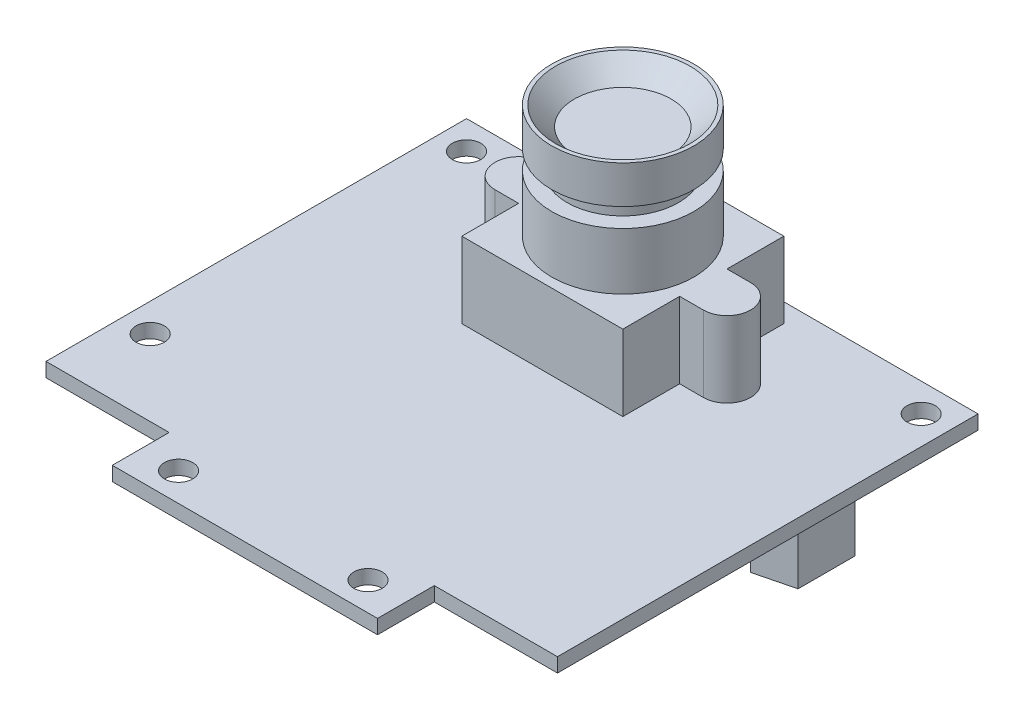
SolidWorks part; units mm, degrees
ref_plane "Front Plane" through (0, 0, 0) normal (0, 0, 1) x (1, 0, 0)
ref_plane "Top Plane" through (0, 0, 0) normal (0, 1, 0) x (1, 0, 0)
ref_plane "Right Plane" through (0, 0, 0) normal (1, 0, 0) x (0, 0, -1)
sketch "Sketch1" plane through (0, 0, 0) normal (0, 1, 0) x (1, 0, 0)
  line L1 (-27, 22.2) -> (27, 22.2)
  line L2 (-27, 22.2) -> (-27, -22.2)
  line L3 (-27, -22.2) -> (27, -22.2)
  line L4 (27, 22.2) -> (27, -22.2)
  line L5 (-27, 22.2) -> (27, -22.2) construction
  line L6 (-27, -22.2) -> (27, 22.2) construction
  line L7 (-14, -22.2) -> (14, -22.2)
  line L8 (-14, -22.2) -> (-14, -28.2)
  line L9 (-14, -28.2) -> (14, -28.2)
  line L10 (14, -22.2) -> (14, -28.2)
  point P0 (0, 0)
  dimension "D1" = 54
  dimension "D2" = 44.4
  dimension "D3" = 13
  dimension "D4" = 13
  dimension "D5" = 6
extrude "Boss-Extrude1" add sketch "Sketch1" along normal blind 1.5 contours L4 L1 L2 L3 | L10 L3 L8 L9 region at (0, 0, 0) region at (0, 0, 25.2)
sketch "Sketch2" plane through (0, 1.5, 0) normal (0, 1, 0) x (1, 0, 0)
  line L0 (-27, 22.2) -> (-27, -22.2) construction
  line L1 (-27, 22.2) -> (27, 22.2) construction
  line L2 (27, 22.2) -> (27, -22.2) construction
  line L3 (-27, -22.2) -> (-14, -22.2) construction
  line L4 (-14, -28.2) -> (14, -28.2) construction
  line L5 (-14, -22.2) -> (-14, -28.2) construction
  line L6 (14, -22.2) -> (14, -28.2) construction
  circle A0 centre (-24, 19.2) radius 1.5
  circle A1 centre (24, 19.2) radius 1.5
  circle A2 centre (-24, -14.2) radius 1.5
  circle A3 centre (-10, -25.2) radius 1.5
  circle A4 centre (10, -25.2) radius 1.5
  circle A5 centre (0, 11.7) radius 1
  dimension "D1" = 3
  dimension "D2" = 3
  dimension "D3" = 3
  dimension "D4" = 3
  dimension "D5" = 3
  dimension "D12" = 3
  dimension "D16" = 10.5
  dimension "D6" = 3
  dimension "D7" = 3
  dimension "D8" = 3
  dimension "D9" = 3
  dimension "D10" = 3
  dimension "D11" = 8
  dimension "D13" = 4
  dimension "D14" = 4
  dimension "D15" = 3
extrude "Cut-Extrude1" cut sketch "Sketch2" against normal blind 1.5
sketch "Sketch3" plane through (0, 1.5, 0) normal (0, 1, 0) x (1, 0, 0)
  line L0 (-27, 22.2) -> (27, 22.2) construction
  line L1 (-8.5, 20.2) -> (8.5, 20.2)
  line L2 (-8.5, 20.2) -> (-8.5, 14.2)
  line L3 (-8.5, 3.2) -> (8.5, 3.2)
  line L4 (8.5, 20.2) -> (8.5, 14.2)
  line L5 (-8.5, 20.2) -> (8.5, 3.2) construction
  line L6 (-8.5, 3.2) -> (8.5, 20.2) construction
  line L7 (0, 0) -> (0, 11.7) construction
  line L8 (-11, 11.7) -> (11, 11.7) construction
  line L9 (-11, 14.2) -> (-8.5, 14.2)
  line L10 (-11, 9.2) -> (-8.5, 9.2)
  line L11 (11, 14.2) -> (8.5, 14.2)
  line L12 (11, 9.2) -> (8.5, 9.2)
  line L13 (-8.5, 9.2) -> (-8.5, 3.2)
  line L14 (8.5, 9.2) -> (8.5, 3.2)
  arc A0 (-11, 14.2) -> (-11, 9.2) centre (-11, 11.7) ccw
  arc A1 (11, 9.2) -> (11, 14.2) centre (11, 11.7) ccw
  point P0 (0, 11.7)
  dimension "D1" = 2
  dimension "D2" = 17
  dimension "D3" = 17
extrude "Boss-Extrude2" add sketch "Sketch3" along normal blind 8
sketch "Sketch4" plane through (0, 9.5, 0) normal (0, 1, 0) x (1, 0, 0)
  line L0 (0, 20.2) -> (0, 3.2) construction
  line L1 (8.5, 20.2) -> (-8.5, 20.2) construction
  line L2 (-8.5, 3.2) -> (8.5, 3.2) construction
  line L3 (-13.5, 11.7) -> (13.5, 11.7) construction
  arc A0 (-11, 14.2) -> (-11, 9.2) centre (-11, 11.7) ccw construction
  arc A1 (11, 9.2) -> (11, 14.2) centre (11, 11.7) ccw construction
  circle A2 centre (0, 11.7) radius 7.5
  dimension "D1" = 15
extrude "Boss-Extrude3" add sketch "Sketch4" along normal blind 6
sketch "Sketch5" plane through (0, 15.5, 0) normal (0, 1, 0) x (1, 0, 0)
  circle A0 centre (0, 11.7) radius 5.8771
extrude "Boss-Extrude4" add sketch "Sketch5" along normal blind 2
sketch "Sketch6" plane through (0, 17.5, 0) normal (0, 1, 0) x (1, 0, 0)
  circle A0 centre (0, 11.7) radius 7.5
extrude "Boss-Extrude5" add sketch "Sketch6" along normal blind 4
sketch "Sketch7" plane through (0, 21.5, 0) normal (0, 1, 0) x (1, 0, 0)
  circle A0 centre (0, 11.7) radius 5.0974
extrude "Cut-Extrude3" cut sketch "Sketch7" against normal blind 2
chamfer "Chamfer1" distance 2 angle 45 1 edges at (0, 21.5, -6.6026)
sketch "Sketch8" plane through (0, 0, 0) normal (0, -1, 0) x (1, 0, 0)
  line L0 (18, -7.2) -> (18, -15.2)
  line L1 (18, -15.2) -> (22, -14.2)
  line L2 (22, -14.2) -> (22, -8.2)
  line L3 (22, -8.2) -> (18, -7.2)
  line L4 (27, -22.2) -> (27, 22.2) construction
  line L5 (-27, -22.2) -> (27, -22.2) construction
  dimension "D1" = 4
  dimension "D2" = 8
  dimension "D3" = 6
  dimension "D4" = 1
  dimension "D5" = 5
  dimension "D6" = 7
extrude "Boss-Extrude6" add sketch "Sketch8" along normal blind 10
sketch "Sketch9" plane through (0, 0, 0) normal (0, -1, 0) x (1, 0, 0)
  line L0 (-27, -22.2) -> (-27, 22.2) construction
  line L1 (-22.5, 1.8) -> (-13.5, 1.8)
  line L2 (-22.5, 1.8) -> (-22.5, -19.2)
  line L3 (-22.5, -19.2) -> (-13.5, -19.2)
  line L4 (-13.5, 1.8) -> (-13.5, -19.2)
  line L5 (-22.5, 1.8) -> (-13.5, -19.2) construction
  line L6 (-22.5, -19.2) -> (-13.5, 1.8) construction
  line L7 (-27, -22.2) -> (27, -22.2) construction
  point P0 (-18, -8.7)
  dimension "D1" = 21
  dimension "D2" = 9
  dimension "D3" = 4.5
  dimension "D4" = 3
extrude "Boss-Extrude7" add sketch "Sketch9" along normal blind 10
